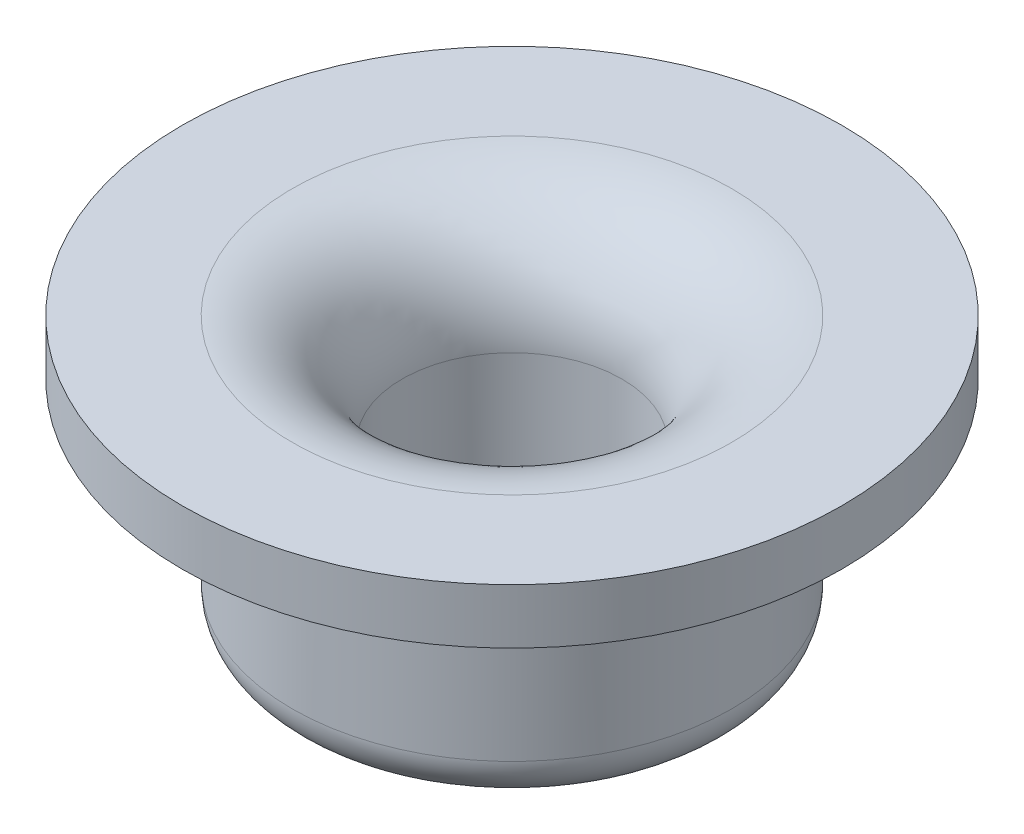
SolidWorks part; units mm, degrees
ref_plane "Front Plane" through (0, 0, 0) normal (0, 0, 1) x (1, 0, 0)
ref_plane "Top Plane" through (0, 0, 0) normal (0, 1, 0) x (1, 0, 0)
ref_plane "Right Plane" through (0, 0, 0) normal (1, 0, 0) x (0, 0, -1)
sketch "Sketch1" plane through (0, 0, 0) normal (1, 0, 0) x (0, 0, -1)
  line L0 (-3.175, 0) -> (-3.175, 7.9375)
  line L1 (-3.175, 7.9375) -> (-9.525, 7.9375)
  line L2 (-9.525, 7.9375) -> (-9.525, 6.35)
  line L3 (-9.525, 6.35) -> (-6.35, 6.35)
  line L4 (-6.35, 6.35) -> (-6.35, 0)
  line L5 (-6.35, 0) -> (-3.175, 0)
  dimension "D1" = 3.175
  dimension "D2" = 6.35
  dimension "D3" = 7.9375
  dimension "D4" = 6.35
  dimension "D5" = 9.525
ref_axis "Axis1" through (0, 0, 0) along (0, 1, 0)
revolve "Revolve1" add sketch "Sketch1" angle 360 about axis through (0, 0, 0) along (0, 1, 0)
fillet "Fillet1" radius 3.175 1 edges at (0, 7.9375, -3.175)
fillet "Fillet4" radius 1.27 2 edges at (0, 0, -6.35) (0, 0, -3.175)
